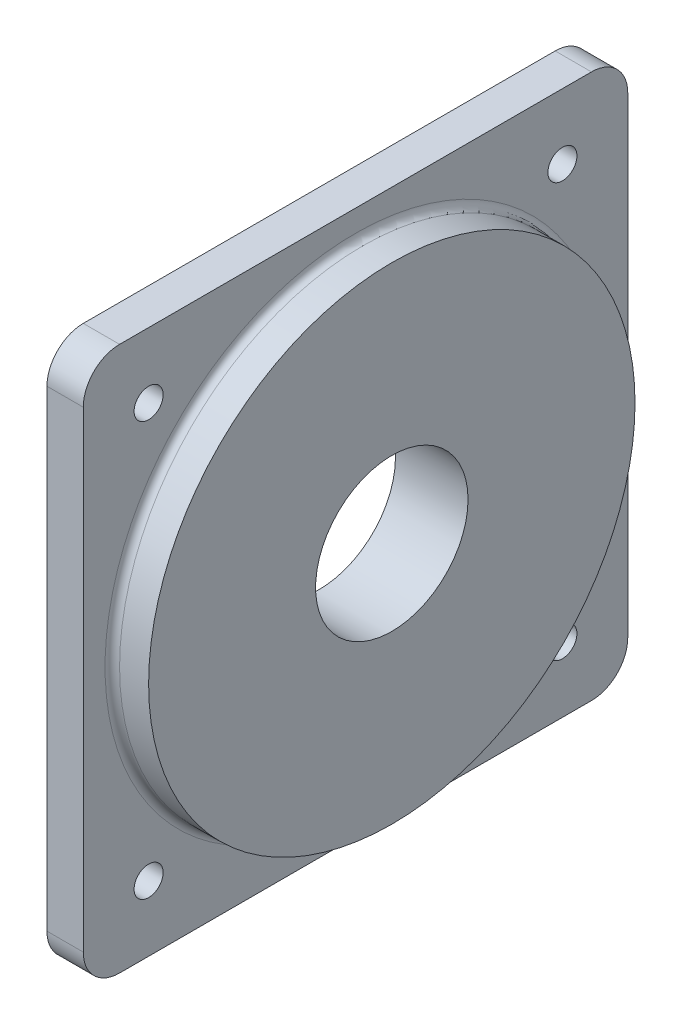
SolidWorks part; units mm, degrees
material "1060-H12"
ref_plane "Front" through (0, 0, 0) normal (0, 0, 1) x (1, 0, 0)
ref_plane "Top" through (0, 0, 0) normal (0, 1, 0) x (1, 0, 0)
ref_plane "Right" through (0, 0, 0) normal (1, 0, 0) x (0, 0, -1)
sketch "Croquis1" plane through (0, 0, 0) normal (1, 0, 0) x (0, 0, -1)
  line L1 (-75, 75) -> (75, 75)
  line L2 (-75, 75) -> (-75, -75)
  line L3 (-75, -75) -> (75, -75)
  line L4 (75, 75) -> (75, -75)
  line L5 (-75, 75) -> (75, -75) construction
  line L6 (-75, -75) -> (75, 75) construction
  point P0 (0, 0)
extrude "Saliente-Extruir1" add sketch "Croquis1" along normal blind 10
sketch "Croquis2" plane through (10, 0, 0) normal (1, 0, 0) x (0, 0, -1)
  circle A0 centre (0, 0) radius 67
  dimension "D1" = 134
extrude "Saliente-Extruir2" add sketch "Croquis2" along normal blind 10
fillet "Redondeo1" radius 10 4 edges at (5, -75, 75) (5, -75, -75) (5, 75, -75) (5, 75, 75)
fillet "Redondeo2" radius 2 1 edges at (10, 0, -67)
sketch "Croquis3" plane through (20, 0, 0) normal (1, 0, 0) x (0, 0, -1)
  line L0 (57, 0) -> (-57, 0) construction
  line L1 (57, -57) -> (-57, -57) construction
  line L2 (57, -57) -> (57, 57) construction
  line L3 (57, 57) -> (-57, 57) construction
  line L4 (-57, -57) -> (-57, 57) construction
  line L5 (57, -57) -> (-57, 57) construction
  line L6 (57, 57) -> (-57, -57) construction
  line L7 (-57, 0) -> (0, -57) construction
  line L8 (0, -57) -> (0, 57) construction
  circle A0 centre (0, 0) radius 21
  circle A1 centre (57, 57) radius 4
  circle A2 centre (57, -57) radius 4
  circle A3 centre (-57, -57) radius 4
  circle A4 centre (-57, 57) radius 4
  dimension "D1" = 42
extrude "Cortar-Extruir1" cut sketch "Croquis3" against normal through all
